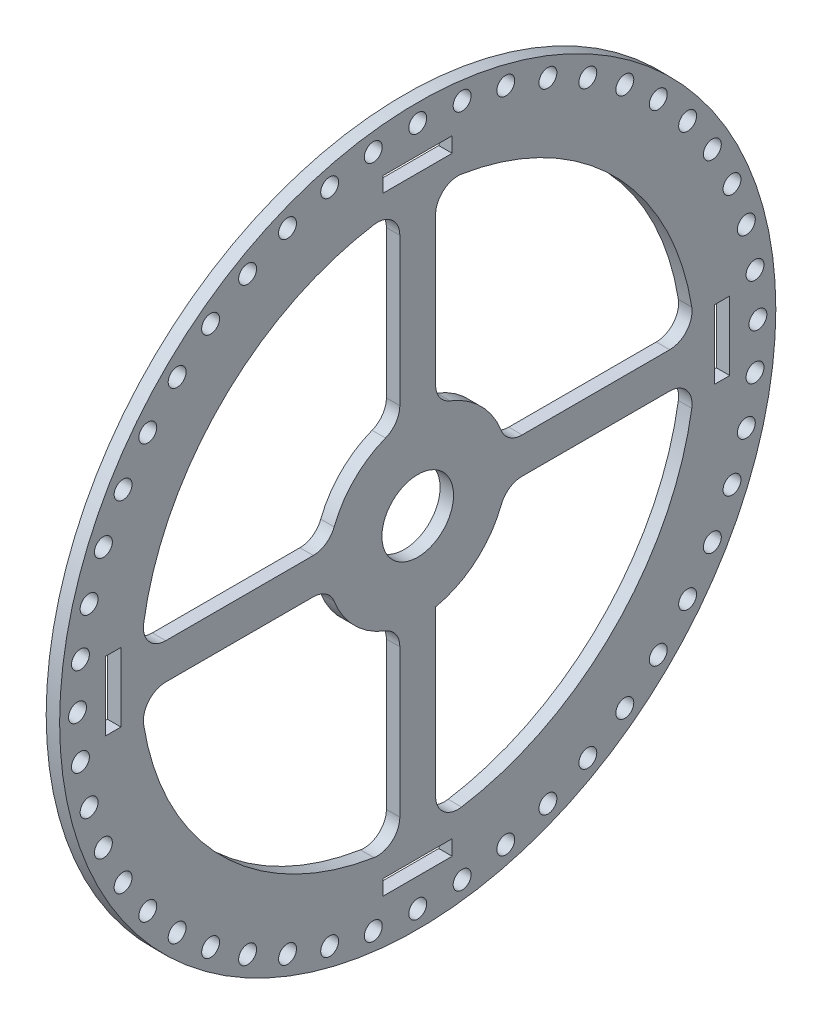
SolidWorks part; units mm, degrees
material "AISI 304"
ref_plane "Front Plane" through (0, 0, 0) normal (0, 0, 1) x (1, 0, 0)
ref_plane "Top Plane" through (0, 0, 0) normal (0, 1, 0) x (1, 0, 0)
ref_plane "Right Plane" through (0, 0, 0) normal (1, 0, 0) x (0, 0, -1)
sketch "Sketch3" plane through (0, 0, 0) normal (1, 0, 0) x (0, 0, -1)
  line L0 (9.798, 2) -> (30.9354, 2)
  line L9 (-30.9354, 2) -> (-9.798, 2)
  line L11 (-30.9354, -2) -> (-9.798, -2)
  line L13 (9.798, -2) -> (30.9354, -2)
  line L14 (-2, -9.798) -> (-2, -30.9354)
  line L16 (-2, 30.9354) -> (-2, 9.798)
  line L18 (2, 30.9354) -> (2, 9.798)
  line L19 (2, -9.798) -> (2, -30.9354)
  line L20 (0, 0) -> (0, 40) construction
  line L22 (3.85, 34.85) -> (-3.85, 34.85)
  line L23 (3.85, 34.85) -> (3.85, 33.15)
  line L24 (3.85, 33.15) -> (-3.85, 33.15)
  line L25 (-3.85, 34.85) -> (-3.85, 33.15)
  line L26 (3.85, 34.85) -> (-3.85, 33.15) construction
  line L27 (3.85, 33.15) -> (-3.85, 34.85) construction
  line L39 (33.15, -3.85) -> (33.15, 3.85)
  line L40 (34.85, 3.85) -> (33.15, 3.85)
  line L41 (34.85, -3.85) -> (34.85, 3.85)
  line L42 (34.85, -3.85) -> (33.15, -3.85)
  line L43 (-3.85, -33.15) -> (3.85, -33.15)
  line L44 (3.85, -34.85) -> (3.85, -33.15)
  line L45 (-3.85, -34.85) -> (3.85, -34.85)
  line L46 (-3.85, -34.85) -> (-3.85, -33.15)
  line L47 (-33.15, 3.85) -> (-33.15, -3.85)
  line L48 (-34.85, -3.85) -> (-33.15, -3.85)
  line L49 (-34.85, 3.85) -> (-34.85, -3.85)
  line L50 (-34.85, 3.85) -> (-33.15, 3.85)
  circle A0 centre (0, 0) radius 40
  arc A1 (30.9354, 2) -> (2, 30.9354) centre (0, 0) ccw
  arc A2 (9.798, 2) -> (2, 9.798) centre (0, 0) ccw
  arc A3 (-9.798, -2) -> (-2, -9.798) centre (0, 0) ccw
  arc A4 (-30.9354, -2) -> (-2, -30.9354) centre (0, 0) ccw
  arc A5 (2, -30.9354) -> (30.9354, -2) centre (0, 0) ccw
  arc A6 (2, -9.798) -> (9.798, -2) centre (0, 0) ccw
  arc A7 (-2, 9.798) -> (-9.798, 2) centre (0, 0) ccw
  arc A8 (-2, 30.9354) -> (-30.9354, 2) centre (0, 0) ccw
  circle A9 centre (0, 0) radius 4
  point P20 (0, 34)
  point P41 (1.15, 0)
  point P42 (0, 0)
  dimension "D1" = 80
  dimension "D2" = 62
  dimension "D5" = 20
  dimension "D8" = 8
  dimension "D3" = 4
  dimension "D4" = 2
  dimension "D6" = 2
  dimension "D7" = 4
  dimension "D9" = 6
  dimension "D10" = 7.7
  dimension "D11" = 1.7
  dimension "D12" = 4
extrude "Boss-Extrude2" add sketch "Sketch3" along normal blind 1.5
sketch "Sketch4" plane through (0, 0, 0) normal (-1, 0, 0) x (0, 0, 1)
  line L0 (0, 0) -> (0, 38) construction
  circle A0 centre (0, 38) radius 1
  point P2 (0, 21.5438)
  dimension "D1" = 2
  dimension "D2" = 38
extrude "Cut-Extrude1" cut sketch "Sketch4" against normal blind 1.5 contours A0
pattern_circular "CirPattern1" count 48 over 360 about axis through (0, 0, 0) along (1, 0, 0) of "Cut-Extrude1"
fillet "Fillet1" radius 2.5 15 edges at (0.75, -2, 30.9354) (0.75, -30.9354, 2) (0.75, -9.798, 2) (0.75, -2, 9.798) (0.75, -30.9354, -2) (0.75, -2, -30.9354) (0.75, 2, -9.798) (0.75, 2, -30.9354) (0.75, 2, 9.798) (0.75, 2, 30.9354) (0.75, 9.798, 2) (0.75, 30.9354, 2) (0.75, 9.798, -2) (0.75, 30.9354, -2) (0.75, -2, -9.798)
